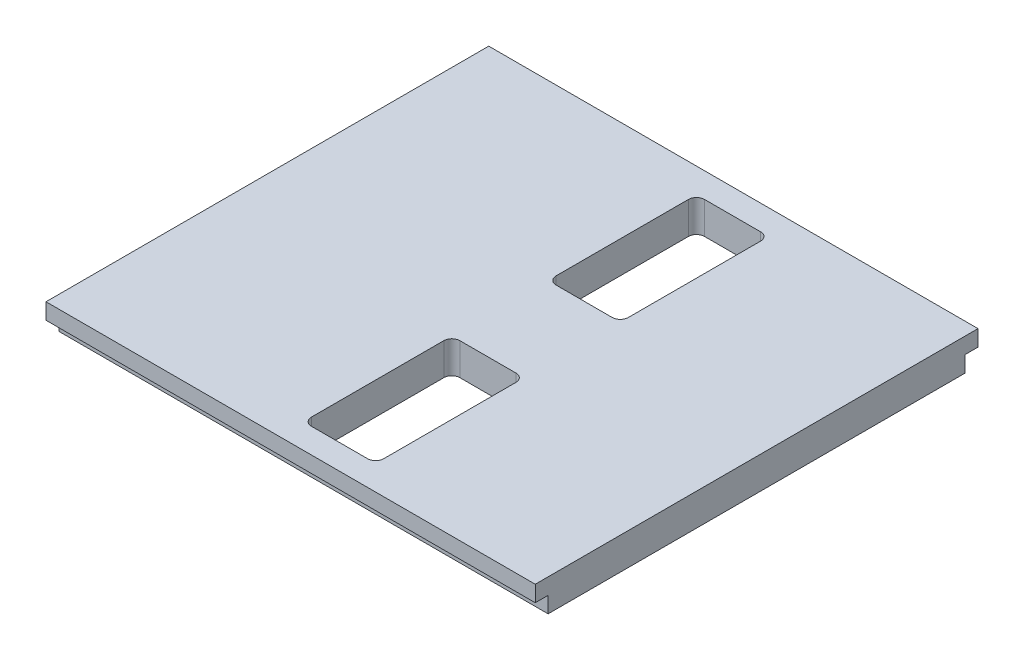
SolidWorks part; units mm, degrees
material "PE High Density"
ref_plane "Front Plane" through (0, 0, 0) normal (0, 0, 1) x (1, 0, 0)
ref_plane "Top Plane" through (0, 0, 0) normal (0, 1, 0) x (1, 0, 0)
ref_plane "Right Plane" through (0, 0, 0) normal (1, 0, 0) x (0, 0, -1)
sketch "Sketch1" plane through (0, 0, 0) normal (1, 0, 0) x (0, 0, -1)
  line L1 (-87.63, -6.35) -> (87.63, -6.35)
  line L2 (-87.63, -6.35) -> (-87.63, 6.35)
  line L3 (-87.63, 6.35) -> (87.63, 6.35)
  line L4 (87.63, -6.35) -> (87.63, 6.35)
  line L5 (-87.63, -6.35) -> (87.63, 6.35) construction
  line L6 (-87.63, 6.35) -> (87.63, -6.35) construction
  point P0 (0, 0)
  dimension "D1" = 175.26
  dimension "D2" = 12.7
extrude "Boss-Extrude1" add sketch "Sketch1" along normal mid plane 193.675
sketch "Sketch2" plane through (96.8375, 0, 0) normal (1, 0, 0) x (0, 0, -1)
  line L0 (87.63, 6.35) -> (-87.63, 6.35) construction
  line L1 (-87.63, -6.35) -> (-82.55, -6.35)
  line L2 (-87.63, -6.35) -> (-87.63, 0)
  line L3 (-87.63, 0) -> (-82.55, 0)
  line L4 (-82.55, -6.35) -> (-82.55, 0)
  line L5 (87.63, -6.35) -> (82.55, -6.35)
  line L6 (87.63, -6.35) -> (87.63, 0)
  line L7 (87.63, 0) -> (82.55, 0)
  line L8 (82.55, -6.35) -> (82.55, 0)
  dimension "D1" = 6.35
  dimension "D2" = 165.1
extrude "Cut-Extrude1" cut sketch "Sketch2" against normal through all
sketch "Sketch3" plane through (0, -6.35, 0) normal (0, 1, 0) x (1, 0, 0)
  line L0 (96.8375, 87.63) -> (96.8375, -87.63) construction
  line L1 (28.448, 11.2395) -> (41.402, 11.2395)
  line L2 (28.448, 4.6355) -> (28.448, -4.6355)
  line L3 (28.448, -11.2395) -> (41.402, -11.2395)
  line L4 (41.402, 4.6355) -> (41.402, -4.6355)
  line L5 (-22.352, 11.2395) -> (-9.398, 11.2395)
  line L6 (-9.398, 4.6355) -> (-9.398, -4.6355)
  line L7 (-22.352, -11.2395) -> (-9.398, -11.2395)
  line L8 (-22.352, 4.6355) -> (-22.352, -4.6355)
  line L17 (28.448, 11.2395) -> (-22.352, 11.2395) construction
  arc A0 (28.448, 11.2395) -> (28.448, 4.6355) centre (28.448, 7.9375) ccw
  arc A1 (28.448, -4.6355) -> (28.448, -11.2395) centre (28.448, -7.9375) ccw
  arc A2 (41.402, -11.2395) -> (41.402, -4.6355) centre (41.402, -7.9375) ccw
  arc A3 (41.402, 4.6355) -> (41.402, 11.2395) centre (41.402, 7.9375) ccw
  arc A4 (-9.398, 4.6355) -> (-9.398, 11.2395) centre (-9.398, 7.9375) ccw
  arc A5 (-9.398, -11.2395) -> (-9.398, -4.6355) centre (-9.398, -7.9375) ccw
  arc A6 (-22.352, -4.6355) -> (-22.352, -11.2395) centre (-22.352, -7.9375) ccw
  arc A7 (-22.352, 11.2395) -> (-22.352, 4.6355) centre (-22.352, 7.9375) ccw
  point P11 (34.925, 11.2395)
  point P15 (41.402, 0)
  point P16 (96.8375, 0)
  dimension "D3" = 6.604
  dimension "D1" = 12.954
  dimension "D2" = 22.479
  dimension "D4" = 61.9125
  dimension "D8" = 50.8
  dimension "D6" = 2
  dimension "D7" = 1
extrude "Cut-Extrude2" cut sketch "Sketch3" along normal blind 6.35
sketch "Sketch5" plane through (0, 6.35, 0) normal (0, 1, 0) x (1, 0, 0)
  line L0 (96.8375, 87.63) -> (96.8375, -87.63) construction
  line L1 (23.8125, -77.7875) -> (-4.7625, -77.7875)
  line L2 (23.8125, -77.7875) -> (23.8125, -19.05)
  line L3 (23.8125, -19.05) -> (-4.7625, -19.05)
  line L4 (-4.7625, -77.7875) -> (-4.7625, -19.05)
  line L5 (23.8125, -77.7875) -> (-4.7625, -19.05) construction
  line L6 (23.8125, -19.05) -> (-4.7625, -77.7875) construction
  line L7 (23.8125, 77.7875) -> (-4.7625, 77.7875)
  line L8 (23.8125, 77.7875) -> (23.8125, 19.05)
  line L9 (23.8125, 19.05) -> (-4.7625, 19.05)
  line L10 (-4.7625, 77.7875) -> (-4.7625, 19.05)
  line L11 (23.8125, 77.7875) -> (-4.7625, 19.05) construction
  line L12 (23.8125, 19.05) -> (-4.7625, 77.7875) construction
  point P0 (9.525, -48.4187)
  point P5 (9.525, 48.4187)
  point P12 (96.8375, 0)
  dimension "D1" = 28.575
  dimension "D2" = 58.7375
  dimension "D3" = 96.8375
  dimension "D4" = 48.4187
  dimension "D5" = 87.3125
extrude "Cut-Extrude4" cut sketch "Sketch5" against normal through all
fillet "Fillet1" radius 3.175 8 edges at (23.8125, 0, -19.05) (23.8125, 0, -77.7875) (-4.7625, 0, -77.7875) (-4.7625, 0, -19.05) (23.8125, 0, 77.7875) (23.8125, 0, 19.05) (-4.7625, 0, 19.05) (-4.7625, 0, 77.7875)
equation "\"D1@Boss-Extrude1\"=7.66629343in "
equation "\"D4@Sketch5\"=\"D3@Sketch5\"/2"
